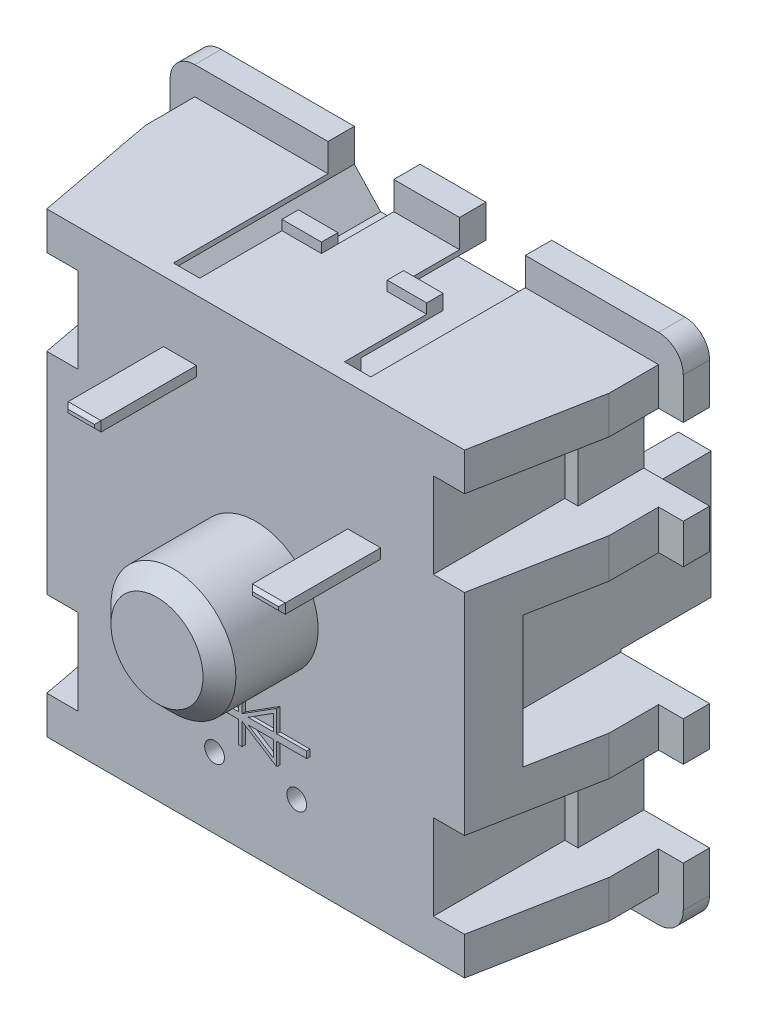
SolidWorks part; units mm, degrees
ref_plane "Front Plane" through (0, 0, 0) normal (0, 0, 1) x (1, 0, 0)
ref_plane "Top Plane" through (0, 0, 0) normal (0, 1, 0) x (1, 0, 0)
ref_plane "Right Plane" through (0, 0, 0) normal (1, 0, 0) x (0, 0, -1)
sketch "Sketch1" plane through (0, 0, 0) normal (0, 0, 1) x (1, 0, 0)
  line L1 (-7.8, 7.8) -> (7.8, 7.8)
  line L2 (-7.8, 7.8) -> (-7.8, -7.8)
  line L3 (-7.8, -7.8) -> (7.8, -7.8)
  line L4 (7.8, 7.8) -> (7.8, -7.8)
  line L5 (-7.8, 7.8) -> (7.8, -7.8) construction
  line L6 (-7.8, -7.8) -> (7.8, 7.8) construction
  point P0 (0, 0)
  dimension "D1" = 15.6
extrude "Boss-Extrude1" add sketch "Sketch1" along normal blind 6
sketch "Sketch2" plane through (0, 0, 6) normal (0, 0, 1) x (1, 0, 0)
  circle A0 centre (0, 0) radius 1.9
  dimension "D1" = 3.8
extrude "Boss-Extrude2" add sketch "Sketch2" along normal blind 3
chamfer "Chamfer1" distance 0.5 angle 45 1 edges at (1.9, 0, 9)
sketch "Sketch4" plane through (0, 0, 6) normal (0, 0, 1) x (1, 0, 0)
  line L0 (7.8, 7.8) -> (-7.8, 7.8) construction
  line L1 (-2.8, 5.1) -> (-1.8, 5.1)
  line L2 (-2.8, 5.1) -> (-2.8, 4.8)
  line L3 (-2.8, 4.8) -> (-1.8, 4.8)
  line L4 (-1.8, 5.1) -> (-1.8, 4.8)
  line L5 (2.8, 3.1) -> (3.8, 3.1)
  line L6 (2.8, 3.1) -> (2.8, 2.8)
  line L7 (2.8, 2.8) -> (3.8, 2.8)
  line L8 (3.8, 3.1) -> (3.8, 2.8)
  line L9 (-7.8, 7.8) -> (-7.8, -7.8) construction
  line L10 (7.8, -7.8) -> (7.8, 7.8) construction
  dimension "D1" = 0.3
  dimension "D2" = 1
  dimension "D3" = 3
  dimension "D4" = 6
  dimension "D5" = 5
  dimension "D6" = 5
extrude "Boss-Extrude3" add sketch "Sketch4" along normal blind 3
chamfer "Chamfer2" distance 0.1 angle 45 8 edges at (3.3, 3.1, 9) (3.8, 2.95, 9) (3.3, 2.8, 9) (2.8, 2.95, 9) (-2.3, 5.1, 9) (-1.8, 4.95, 9) (-2.3, 4.8, 9) (-2.8, 4.95, 9)
sketch "Sketch6" plane through (0, 7.8, 0) normal (0, 1, 0) x (1, 0, 0)
  line L0 (-7.8, -0.8) -> (-7.8, -6)
  line L1 (-7.8, -6) -> (-7.8, 0) construction
  line L2 (-7.8, -0.8) -> (-7.05, -0.8)
  line L3 (-7.05, -0.8) -> (-7.05, -2.3)
  line L4 (-7.05, -2.3) -> (-6.35, -6)
  line L5 (-6.35, -6) -> (-7.8, -6)
  line L6 (7.8, -6) -> (-7.8, -6) construction
  line L7 (7.8, 0) -> (-7.8, 0) construction
  dimension "D1" = 0.8
  dimension "D2" = 1.5
  dimension "D3" = 0.75
  dimension "D4" = 1.45
extrude "Cut-Extrude2" cut sketch "Sketch6" against normal through all
mirror "Mirror1" about plane through (0, 0, 0) normal (1, 0, 0) of "Cut-Extrude2"
sketch "Sketch7" plane through (-7.8, 0, 0) normal (-1, 0, 0) x (0, 0, 1)
  line L0 (0, 7.8) -> (0, -7.8) construction
  line L1 (0, 3.2) -> (6, 3.2)
  line L2 (0, 3.2) -> (0, 5.8)
  line L3 (0, 5.8) -> (6, 5.8)
  line L4 (6, 3.2) -> (6, 5.8)
  line L5 (6, -7.8) -> (6, 7.8) construction
  line L6 (0.8, 7.8) -> (0, 7.8) construction
  dimension "D1" = 2.6
  dimension "D2" = 2
extrude "Cut-Extrude3" cut sketch "Sketch7" against normal blind 2
sketch "Sketch8" plane through (-5.8, 0, 0) normal (-1, 0, 0) x (0, 0, 1)
  line L0 (0, 3.2) -> (6, 3.2) construction
  line L1 (2, 3.2) -> (6, 3.2)
  line L2 (2, 3.2) -> (2, 5.8)
  line L3 (2, 5.8) -> (6, 5.8)
  line L4 (6, 3.2) -> (6, 5.8)
  line L5 (0, 5.8) -> (0, 3.2) construction
  dimension "D1" = 2
extrude "Cut-Extrude4" cut sketch "Sketch8" against normal blind 0.4
mirror "Mirror2" about plane through (0, 0, 0) normal (0, 1, 0) of "Cut-Extrude4", "Cut-Extrude3"
mirror "Mirror3" about plane through (0, 0, 0) normal (1, 0, 0) of "Mirror2"
sketch "Sketch9" plane through (-7.8, 0, 0) normal (-1, 0, 0) x (0, 0, 1)
  line L0 (0, 3.2) -> (0, -3.2) construction
  line L1 (0, -2) -> (4.5, -2)
  line L2 (0, -2) -> (0, 2)
  line L3 (0, 2) -> (4.5, 2)
  line L4 (4.5, -2) -> (4.5, 2)
  point P6 (4.5, 0)
  dimension "D1" = 4
  dimension "D2" = 4.5
extrude "Cut-Extrude5" cut sketch "Sketch9" against normal blind 2.7
mirror "Mirror4" about plane through (0, 0, 0) normal (1, 0, 0) of "Cut-Extrude5"
shell "Shell1" thickness 1 removed face at (0, 0, 0)
sketch "Sketch3" plane through (0, 0, 6) normal (0, 0, 1) x (1, 0, 0)
  line L0 (-6.35, -7.8) -> (6.35, -7.8) construction
  line L1 (-1.25, -4.8) -> (1.25, -4.8) construction
  circle A0 centre (-1.25, -4.8) radius 0.3
  circle A1 centre (1.25, -4.8) radius 0.3
  point P6 (0, -4.8)
  dimension "D3" = 0.6
  dimension "D1" = 3
  dimension "D2" = 2.5
extrude "Cut-Extrude1" cut sketch "Sketch3" against normal through all
sketch "Sketch10" plane through (0, 0, 0) normal (0, 0, -1) x (-1, 0, 0)
  line L0 (4.1, 3) -> (4.1, -3) construction
  line L1 (4.1, 1.925) -> (5.1, 1.925)
  line L2 (4.1, 1.925) -> (4.1, -1.925)
  line L3 (4.1, -1.925) -> (5.1, -1.925)
  line L4 (5.1, 1.925) -> (5.1, -1.925)
  line L5 (5.1, 2) -> (5.1, -2) construction
  point P8 (5.1, 0)
  dimension "D1" = 3.85
extrude "Boss-Extrude4" add sketch "Sketch10" along normal blind 3
mirror "Mirror5" about plane through (0, 0, 0) normal (1, 0, 0) of "Boss-Extrude4"
chamfer "Chamfer3" distance 0.25 angle 45 8 edges at (-4.6, 1.925, -3) (-5.1, 0, -3) (-4.6, -1.925, -3) (-4.1, 0, -3) (4.6, -1.925, -3) (5.1, 0, -3) (4.6, 1.925, -3) (4.1, 0, -3)
sketch "Sketch11" plane through (-7.8, 0, 0) normal (-1, 0, 0) x (0, 0, 1)
  line L1 (0.8, 7.8) -> (6, 7.8)
  line L2 (0.8, 7.8) -> (0.8, 6.95)
  line L3 (0.8, 6.95) -> (6, 6.95)
  line L4 (6, 7.8) -> (6, 6.95)
  dimension "D1" = 0.85
extrude "Cut-Extrude6" cut sketch "Sketch11" against normal through all
mirror "Mirror6" about plane through (0, 0, 0) normal (0, 1, 0) of "Cut-Extrude6"
fillet "Fillet1" radius 0.75 4 edges at (7.8, 7.8, 0.4) (7.8, -7.8, 0.4) (-7.8, 7.8, 0.4) (-7.8, -7.8, 0.4)
sketch "Sketch12" plane through (0, 7.8, 0) normal (0, 1, 0) x (1, 0, 0)
  line L0 (7.05, 0) -> (-7.05, 0) construction
  line L1 (-3, 0) -> (-1, 0)
  line L2 (-3, 0) -> (-3, -2.5)
  line L3 (-3, -2.5) -> (-1, -2.5)
  line L4 (-1, 0) -> (-1, -2.5)
  dimension "D1" = 1
  dimension "D2" = 2
  dimension "D3" = 2.5
extrude "Cut-Extrude7" cut sketch "Sketch12" against normal up to next
sketch "Sketch13" plane through (0, 6.95, 0) normal (0, 1, 0) x (1, 0, 0)
  line L1 (-3, -2.5) -> (-2.2, -2.5)
  line L2 (-3, -2.5) -> (-3, -5.5)
  line L3 (-3, -5.5) -> (-2.2, -5.5)
  line L4 (-2.2, -2.5) -> (-2.2, -5.5)
  dimension "D1" = 0.8
  dimension "D2" = 3
extrude "Cut-Extrude8" cut sketch "Sketch13" against normal blind 1
mirror "Mirror7" about plane through (0, 0, 0) normal (1, 0, 0) of "Cut-Extrude8", "Cut-Extrude7"
mirror "Mirror8" about plane through (0, 0, 0) normal (0, 1, 0) of "Mirror7"
sketch "Sketch14" plane through (0, 0, 5) normal (0, 0, -1) x (-1, 0, 0)
  line L0 (-4.8, -6.8) -> (-4.8, -3) construction
  line L1 (-4.8, -3.3) -> (4.8, -3.3)
  line L2 (-4.8, -3.3) -> (-4.8, -4.3)
  line L3 (-4.8, -4.3) -> (4.8, -4.3)
  line L4 (4.8, -3.3) -> (4.8, -4.3)
  line L5 (4.8, -6.8) -> (4.8, -3) construction
  line L6 (-3, -6.8) -> (-4.8, -6.8) construction
  dimension "D1" = 2.5
  dimension "D2" = 1
extrude "Boss-Extrude5" add sketch "Sketch14" along normal up to vertex (5 mm away) up to point (4.8, -3, 0)
sketch "Sketch15" plane through (0, 0, 8) normal (0, 0, -1) x (-1, 0, 0)
  circle A1 centre (0, 0) radius 1.5
  circle A2 centre (0, 0) radius 1
  dimension "D1" = 3
  dimension "D2" = 2
extrude "Boss-Extrude6" add sketch "Sketch15" along normal blind 7
chamfer "Chamfer4" distance 0.25 angle 45 1 edges at (-1.5, 0, 1)
sketch "Sketch16" plane through (0, 0, 5) normal (0, 0, -1) x (-1, 0, 0)
  line L0 (-3, 6.8) -> (-2.2, 5.95)
  line L1 (-2.2, 5.95) -> (2.2, 5.95)
  line L2 (2.2, 5.95) -> (3, 6.8)
  line L3 (3, 6.8) -> (3.3, 6.8)
  line L4 (3, 6.8) -> (4.8, 6.8) construction
  line L5 (-3, 6.8) -> (-3.3, 6.8)
  line L6 (-3.0864, 6.6) -> (-3.3, 6.6)
  line L7 (-3.0864, 6.6) -> (-2.2864, 5.75)
  line L8 (-2.2864, 5.75) -> (2.2864, 5.75)
  line L9 (2.2864, 5.75) -> (3.0864, 6.6)
  line L10 (3.0864, 6.6) -> (3.3, 6.6)
  line L11 (-3, 6.8) -> (-3.3, 6.8) construction
  line L12 (-4.8, 6.8) -> (-3, 6.8) construction
  line L13 (-3.3, 6.6) -> (-3.3, 6.8)
  line L14 (3.3, 6.8) -> (3.3, 6.6)
  dimension "D2" = 0.3
  dimension "D3" = 0.3
  dimension "D1" = 0.2
extrude "Boss-Extrude7" add sketch "Sketch16" along normal blind 5 and the other way blind 1
sketch "Sketch17" plane through (0, -6.95, 0) normal (0, -1, 0) x (1, 0, 0)
  line L1 (2.2, 2.5) -> (1, 2.5)
  line L2 (2.2, 2.5) -> (2.2, 3)
  line L3 (2.2, 3) -> (1, 3)
  line L4 (1, 2.5) -> (1, 3)
  dimension "D1" = 0.5
extrude "Boss-Extrude8" add sketch "Sketch17" along normal blind 0.3
mirror "Mirror9" about plane through (0, 0, 0) normal (1, 0, 0) of "Boss-Extrude8"
mirror "Mirror10" about plane through (0, 0, 0) normal (0, 1, 0) of "Mirror9"
sketch "Sketch18" plane through (0, 0, 6) normal (0, 0, 1) x (1, 0, 0)
  line L0 (-1.2264, -3.2739) -> (1.6521, -3.2739)
  line L1 (-0.3142, -3.2739) -> (-0.3142, -2.6049)
  line L2 (-0.3142, -3.2739) -> (0.7399, -2.6049)
  line L3 (0.7399, -2.6049) -> (0.7399, -3.2739)
extrude "Extrude-Thin1" add sketch "Sketch18" along normal blind 0.1 thin thin type one direction wall 0.1
mirror "Mirror11" about plane through (-1.2264, -3.3739, 6.1) normal (0, 1, 0) of "Extrude-Thin1"
